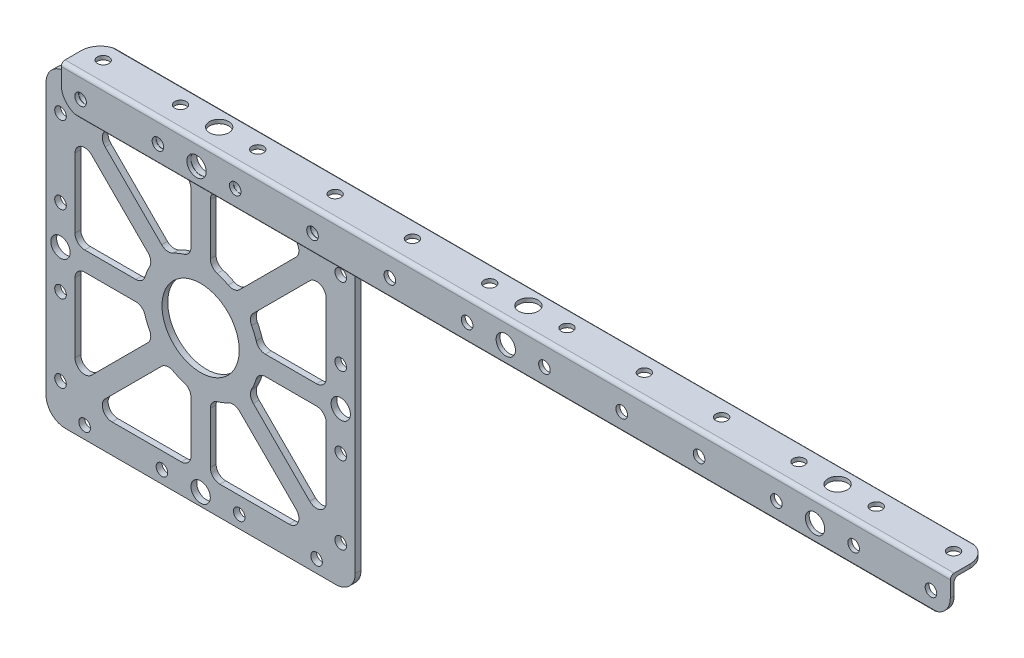
SolidWorks part; units mm, degrees
material "Fibra de vidrio-A"
ref_plane "Alzado" through (0, 0, 0) normal (0, 0, 1) x (1, 0, 0)
ref_plane "Planta" through (0, 0, 0) normal (0, 1, 0) x (1, 0, 0)
ref_plane "Vista lateral" through (0, 0, 0) normal (1, 0, 0) x (0, 0, -1)
sketch "Croquis1" plane through (0, 0, 0) normal (0, 0, 1) x (1, 0, 0)
  line L1 (-35, -40) -> (35, -40)
  line L2 (-40, -35) -> (-40, 35)
  line L3 (-35, 40) -> (35, 40)
  line L4 (40, -35) -> (40, 35)
  line L5 (-40, -40) -> (40, 40) construction
  line L6 (-40, 40) -> (40, -40) construction
  arc A0 (35, 40) -> (40, 35) centre (35, 35) cw
  arc A1 (35, -40) -> (40, -35) centre (35, -35) ccw
  arc A2 (-35, -40) -> (-40, -35) centre (-35, -35) cw
  arc A3 (-40, 35) -> (-35, 40) centre (-35, 35) cw
  point P0 (0, 0)
  dimension "D2" = 5
  dimension "D1" = 80
extrude "Saliente-Extruir1" add sketch "Croquis1" along normal blind 1.5
sketch "Croquis2" plane through (0, 0, 1.5) normal (0, 0, 1) x (1, 0, 0)
  line L0 (0, 0) -> (0, 40) construction
  line L1 (35, 40) -> (-35, 40) construction
  line L2 (0, 0) -> (40, 0) construction
  line L3 (40, -35) -> (40, 35) construction
  line L4 (2.5, 16.7705) -> (2.5, 30)
  line L5 (0, 0) -> (38.5355, 38.5355) construction
  line L6 (10.0908, 13.6263) -> (24.6967, 28.2322)
  line L7 (5, 32.5) -> (22.9289, 32.5)
  line L8 (-10.0908, 13.6263) -> (-24.6967, 28.2322)
  line L9 (-5, 32.5) -> (-22.9289, 32.5)
  line L10 (-2.5, 16.7705) -> (-2.5, 30)
  line L11 (32.5, 5) -> (32.5, 22.9289)
  line L12 (16.7705, 2.5) -> (30, 2.5)
  line L13 (13.6263, 10.0908) -> (28.2322, 24.6967)
  line L14 (16.7705, -2.5) -> (30, -2.5)
  line L15 (32.5, -5) -> (32.5, -22.9289)
  line L16 (13.6263, -10.0908) -> (28.2322, -24.6967)
  line L17 (5, -32.5) -> (22.9289, -32.5)
  line L18 (2.5, -16.7705) -> (2.5, -30)
  line L19 (10.0908, -13.6263) -> (24.6967, -28.2322)
  line L20 (-2.5, -16.7705) -> (-2.5, -30)
  line L21 (-5, -32.5) -> (-22.9289, -32.5)
  line L22 (-10.0908, -13.6263) -> (-24.6967, -28.2322)
  line L23 (-32.5, -5) -> (-32.5, -22.9289)
  line L24 (-16.7705, -2.5) -> (-30, -2.5)
  line L25 (-13.6263, -10.0908) -> (-28.2322, -24.6967)
  line L26 (-16.7705, 2.5) -> (-30, 2.5)
  line L27 (-32.5, 5) -> (-32.5, 22.9289)
  line L28 (-13.6263, 10.0908) -> (-28.2322, 24.6967)
  circle A0 centre (0, 0) radius 10
  arc A1 (7.134, 13.1949) -> (4.2857, 14.3747) centre (0, 0) ccw
  arc A2 (40, 35) -> (35, 40) centre (35, 35) ccw construction
  circle A3 centre (0, 0) radius 15 construction
  arc A4 (2.5, 16.7705) -> (4.2857, 14.3747) centre (5, 16.7705) ccw
  arc A5 (10.0908, 13.6263) -> (7.134, 13.1949) centre (8.323, 15.3941) cw
  arc A6 (24.6967, 28.2322) -> (22.9289, 32.5) centre (22.9289, 30) ccw
  arc A7 (2.5, 30) -> (5, 32.5) centre (5, 30) cw
  arc A8 (-24.6967, 28.2322) -> (-22.9289, 32.5) centre (-22.9289, 30) cw
  arc A9 (-2.5, 30) -> (-5, 32.5) centre (-5, 30) ccw
  arc A10 (-2.5, 16.7705) -> (-4.2857, 14.3747) centre (-5, 16.7705) cw
  arc A11 (-10.0908, 13.6263) -> (-7.134, 13.1949) centre (-8.323, 15.3941) ccw
  arc A12 (-7.134, 13.1949) -> (-4.2857, 14.3747) centre (0, 0) cw
  arc A13 (28.2322, 24.6967) -> (32.5, 22.9289) centre (30, 22.9289) cw
  arc A14 (30, 2.5) -> (32.5, 5) centre (30, 5) ccw
  arc A15 (16.7705, 2.5) -> (14.3747, 4.2857) centre (16.7705, 5) cw
  arc A16 (13.1949, 7.134) -> (14.3747, 4.2857) centre (0, 0) cw
  arc A17 (13.6263, 10.0908) -> (13.1949, 7.134) centre (15.3941, 8.323) ccw
  arc A18 (13.1949, -7.134) -> (14.3747, -4.2857) centre (0, 0) ccw
  arc A19 (13.6263, -10.0908) -> (13.1949, -7.134) centre (15.3941, -8.323) cw
  arc A20 (16.7705, -2.5) -> (14.3747, -4.2857) centre (16.7705, -5) ccw
  arc A21 (30, -2.5) -> (32.5, -5) centre (30, -5) cw
  arc A22 (28.2322, -24.6967) -> (32.5, -22.9289) centre (30, -22.9289) ccw
  arc A23 (24.6967, -28.2322) -> (22.9289, -32.5) centre (22.9289, -30) cw
  arc A24 (2.5, -30) -> (5, -32.5) centre (5, -30) ccw
  arc A25 (2.5, -16.7705) -> (4.2857, -14.3747) centre (5, -16.7705) cw
  arc A26 (7.134, -13.1949) -> (4.2857, -14.3747) centre (0, 0) cw
  arc A27 (10.0908, -13.6263) -> (7.134, -13.1949) centre (8.323, -15.3941) ccw
  arc A28 (-7.134, -13.1949) -> (-4.2857, -14.3747) centre (0, 0) ccw
  arc A29 (-10.0908, -13.6263) -> (-7.134, -13.1949) centre (-8.323, -15.3941) cw
  arc A30 (-2.5, -16.7705) -> (-4.2857, -14.3747) centre (-5, -16.7705) ccw
  arc A31 (-2.5, -30) -> (-5, -32.5) centre (-5, -30) cw
  arc A32 (-24.6967, -28.2322) -> (-22.9289, -32.5) centre (-22.9289, -30) ccw
  arc A33 (-28.2322, -24.6967) -> (-32.5, -22.9289) centre (-30, -22.9289) cw
  arc A34 (-30, -2.5) -> (-32.5, -5) centre (-30, -5) ccw
  arc A35 (-16.7705, -2.5) -> (-14.3747, -4.2857) centre (-16.7705, -5) cw
  arc A36 (-13.1949, -7.134) -> (-14.3747, -4.2857) centre (0, 0) cw
  arc A37 (-13.6263, -10.0908) -> (-13.1949, -7.134) centre (-15.3941, -8.323) ccw
  arc A38 (-13.1949, 7.134) -> (-14.3747, 4.2857) centre (0, 0) ccw
  arc A39 (-13.6263, 10.0908) -> (-13.1949, 7.134) centre (-15.3941, 8.323) cw
  arc A40 (-16.7705, 2.5) -> (-14.3747, 4.2857) centre (-16.7705, 5) ccw
  arc A41 (-30, 2.5) -> (-32.5, 5) centre (-30, 5) cw
  arc A42 (-28.2322, 24.6967) -> (-32.5, 22.9289) centre (-30, 22.9289) ccw
  point P25 (28.9645, 32.5)
  point P28 (2.5, 32.5)
  point P116 (0, 0)
  dimension "D1" = 20
  dimension "D7" = 2.5
  dimension "D2" = 5
  dimension "D3" = 7.5
  dimension "D4" = 2.5
  dimension "D5" = 5
  dimension "D8" = 4
extrude "Cortar-Extruir1" cut sketch "Croquis2" against normal through all
sketch "Croquis3" plane through (0, 0, 1.5) normal (0, 0, 1) x (1, 0, 0)
  line L0 (-36.25, -40) -> (-36.25, 40) construction
  line L1 (-40, 35) -> (-40, -35) construction
  line L2 (-40, 0) -> (-32.5, 0) construction
  line L3 (35, 40) -> (-35, 40) construction
  line L4 (0, -0.825) -> (0, 0.825) construction
  circle A0 centre (-36.25, 30) radius 1.5
  circle A1 centre (-36.25, 10) radius 1.5
  circle A2 centre (-36.25, -10) radius 1.5
  circle A3 centre (-36.25, -30) radius 1.5
  circle A4 centre (36.25, -30) radius 1.5
  circle A5 centre (36.25, -10) radius 1.5
  circle A6 centre (36.25, 10) radius 1.5
  circle A7 centre (36.25, 30) radius 1.5
  circle A8 centre (-36.25, 0) radius 2.5
  circle A9 centre (36.25, 0) radius 2.5
  point P8 (-36.25, 0)
  dimension "D1" = 3
  dimension "D2" = 10
  dimension "D4" = 5
  dimension "D3" = 4
extrude "Cortar-Extruir2" cut sketch "Croquis3" against normal through all
sketch "Croquis5" plane through (0, 0, 0) normal (1, 0, 0) x (0, 0, -1)
  line L0 (0, 32.5) -> (-1.5, 32.5) construction
  line L2 (-0.75, 32.5) -> (-0.75, 35) construction
  line L3 (-1.5, 35) -> (0, 35) construction
  line L4 (-1.55, 32.75) -> (-1.55, 40)
  line L5 (-1.8, 32.5) -> (-2.3, 32.5)
  line L6 (-2.55, 32.75) -> (-2.55, 40.85)
  line L7 (1.05, 32.75) -> (1.05, 40.85)
  line L8 (0.3, 32.5) -> (0.8, 32.5)
  line L9 (0.05, 32.75) -> (0.05, 40)
  line L10 (-1.3, 40.25) -> (-0.2, 40.25)
  line L11 (-2.05, 41.35) -> (0.55, 41.35)
  arc A0 (1.05, 40.85) -> (0.55, 41.35) centre (0.55, 40.85) ccw
  arc A1 (-2.55, 40.85) -> (-2.05, 41.35) centre (-2.05, 40.85) cw
  arc A2 (0.05, 40) -> (-0.2, 40.25) centre (-0.2, 40) ccw
  arc A3 (-1.55, 40) -> (-1.3, 40.25) centre (-1.3, 40) cw
  arc A4 (1.05, 32.75) -> (0.8, 32.5) centre (0.8, 32.75) cw
  arc A5 (0.3, 32.5) -> (0.05, 32.75) centre (0.3, 32.75) cw
  arc A6 (-1.8, 32.5) -> (-1.55, 32.75) centre (-1.8, 32.75) ccw
  arc A7 (-2.3, 32.5) -> (-2.55, 32.75) centre (-2.3, 32.75) cw
  point P16 (1.05, 41.35)
  point P19 (-2.55, 41.35)
  point P22 (0.05, 40.25)
  point P25 (-1.55, 40.25)
  point P28 (1.05, 32.5)
  point P31 (0.05, 32.5)
  point P34 (-1.55, 32.5)
  point P37 (-2.55, 32.5)
  dimension "D5" = 0.5
  dimension "D6" = 0.25
  dimension "D7" = 0.25
  dimension "D1" = 0.8
  dimension "D2" = 7.75
  dimension "D3" = 1
  dimension "D4" = 8.85
extrude "Saliente-Extruir2" add sketch "Croquis5" along normal mid plane 70 separate body
sketch "Croquis4" plane through (0, 0, 1.5) normal (0, 0, 1) x (1, 0, 0)
  line L0 (0, 40) -> (0, 36.75) construction
  line L1 (35, 40) -> (-35, 40) construction
  line L2 (-40, 36.75) -> (40, 36.75) construction
  line L3 (1.98, 0) -> (-1.98, 0) construction
  circle A0 centre (-30, 36.75) radius 1.5
  circle A1 centre (-10, 36.75) radius 1.5
  circle A2 centre (10, 36.75) radius 1.5
  circle A3 centre (30, 36.75) radius 1.5
  circle A4 centre (10, -36.75) radius 1.5
  circle A5 centre (30, -36.75) radius 1.5
  circle A6 centre (-10, -36.75) radius 1.5
  circle A7 centre (-30, -36.75) radius 1.5
  circle A8 centre (0, 36.75) radius 2.5
  circle A9 centre (0, -36.75) radius 2.5
  point P8 (0, 36.75)
  dimension "D3" = 3
  dimension "D6" = 5
  dimension "D1" = 3.25
  dimension "D2" = 40
  dimension "D4" = 10
  dimension "D5" = 4
extrude "Cortar-Extruir3" cut sketch "Croquis4" against normal through all both and the other way through all
fillet "Redondeo1" radius 5 4 edges at (-35, 32.5, -0.55) (35, 32.5, -0.55) (35, 32.5, 2.05) (-35, 32.5, 2.05)
pattern_circular "MatrizC1" count 2 every 90 about axis through (0, 40.8, 0.75) along (1, 0, 0) of bodies 106
combine bodies "Combinar2" bodies to combine 106 107
sketch "Croquis6" plane through (35, 0, 0) normal (1, 0, 0) x (0, 0, -1)
  line L0 (-2.55, 40.85) -> (-2.55, 41.6)
  line L1 (-1.55, 42.6) -> (-0.8, 42.6)
  line L2 (-0.8, 42.6) -> (-0.8, 40.85)
  line L3 (-0.8, 40.85) -> (-2.55, 40.85)
  arc A0 (-2.55, 41.6) -> (-1.55, 42.6) centre (-1.55, 41.6) cw
  dimension "D1" = 1
extrude "Saliente-Extruir3" add sketch "Croquis6" against normal up to surface (70 mm away) up to face at (-35, 40.1525, 0.1025)
sketch "Croquis7" plane through (35, 0, 0) normal (1, 0, 0) x (0, 0, -1)
  line L9 (0.05, 37.5) -> (0.05, 39)
  line L10 (1.05, 40) -> (2.55, 40)
  line L11 (2.55, 40) -> (2.55, 41.6)
  line L12 (2.55, 41.6) -> (-0.55, 41.6)
  line L13 (-1.55, 40.6) -> (-1.55, 37.5)
  line L14 (-1.55, 37.5) -> (0.05, 37.5)
  arc A0 (-0.55, 41.6) -> (-1.55, 40.6) centre (-0.55, 40.6) ccw
  arc A1 (0.05, 39) -> (1.05, 40) centre (1.05, 39) cw
  point P21 (0.05, 40)
  dimension "D1" = 1
extrude "Cortar-Extruir4" cut sketch "Croquis7" against normal through all
delete or keep bodies "Sólido-Eliminar/Conservar 3" bodies 113
sketch "Croquis10" plane through (0, 0, 0) normal (1, 0, 0) x (0, 0, -1)
  line L0 (7.55, 41.85) -> (7.55, 42.35) construction
  line L1 (7.3, 42.6) -> (2.55, 42.6) construction
  line L2 (2.55, 41.6) -> (7.3, 41.6) construction
  line L3 (-2.3, 32.5) -> (-1.8, 32.5) construction
  line L4 (-1.55, 32.75) -> (-1.55, 37.5) construction
  line L5 (-2.55, 37.5) -> (-2.55, 32.75) construction
  line L6 (-1.55, 37.5) -> (-1.55, 40.6) construction
  line L7 (-0.55, 41.6) -> (2.55, 41.6) construction
  line L8 (2.55, 42.6) -> (-1.55, 42.6) construction
  line L9 (-2.55, 41.6) -> (-2.55, 37.5) construction
  line L10 (7.55, 41.85) -> (7.55, 42.35)
  line L11 (7.3, 42.6) -> (2.55, 42.6)
  line L12 (2.55, 41.6) -> (7.3, 41.6)
  line L13 (-2.3, 32.5) -> (-1.8, 32.5)
  line L14 (-1.55, 32.75) -> (-1.55, 37.5)
  line L15 (-2.55, 37.5) -> (-2.55, 32.75)
  line L16 (-1.55, 37.5) -> (-1.55, 40.6)
  line L17 (-0.55, 41.6) -> (2.55, 41.6)
  line L18 (2.55, 42.6) -> (-1.55, 42.6)
  line L19 (-2.55, 41.6) -> (-2.55, 37.5)
  arc A0 (7.3, 41.6) -> (7.55, 41.85) centre (7.3, 41.85) ccw construction
  arc A1 (7.55, 42.35) -> (7.3, 42.6) centre (7.3, 42.35) ccw construction
  arc A2 (-2.55, 32.75) -> (-2.3, 32.5) centre (-2.3, 32.75) ccw construction
  arc A3 (-1.8, 32.5) -> (-1.55, 32.75) centre (-1.8, 32.75) ccw construction
  arc A4 (-0.55, 41.6) -> (-1.55, 40.6) centre (-0.55, 40.6) ccw construction
  arc A5 (-1.55, 42.6) -> (-2.55, 41.6) centre (-1.55, 41.6) ccw construction
  arc A6 (7.3, 41.6) -> (7.55, 41.85) centre (7.3, 41.85) ccw
  arc A7 (7.55, 42.35) -> (7.3, 42.6) centre (7.3, 42.35) ccw
  arc A8 (-2.55, 32.75) -> (-2.3, 32.5) centre (-2.3, 32.75) ccw
  arc A9 (-1.8, 32.5) -> (-1.55, 32.75) centre (-1.8, 32.75) ccw
  arc A10 (-0.55, 41.6) -> (-1.55, 40.6) centre (-0.55, 40.6) ccw
  arc A11 (-1.55, 42.6) -> (-2.55, 41.6) centre (-1.55, 41.6) ccw
extrude "Saliente-Extruir4" add sketch "Croquis10" along normal blind 195
fillet "Redondeo2" radius 5 2 edges at (195, 32.5, 2.05) (195, 42.1, -7.55)
sketch "Croquis11" plane through (0, 42.6, 0) normal (0, 1, 0) x (1, 0, 0)
  line L0 (-30, 3.3) -> (-35, 3.3) construction
  line L2 (0, 5.8) -> (0, 0.8) construction
  line L3 (190, 3.3) -> (195, 3.3) construction
  circle A0 centre (-30, 3.3) radius 1.5 construction
  circle A1 centre (-30, 3.3) radius 1.5
  circle A2 centre (-10, 3.3) radius 1.5
  circle A3 centre (10, 3.3) radius 1.5
  circle A4 centre (30, 3.3) radius 1.5
  circle A5 centre (50, 3.3) radius 1.5
  circle A6 centre (70, 3.3) radius 1.5
  circle A7 centre (90, 3.3) radius 1.5
  circle A8 centre (110, 3.3) radius 1.5
  circle A9 centre (130, 3.3) radius 1.5
  circle A10 centre (150, 3.3) radius 1.5
  circle A11 centre (170, 3.3) radius 1.5
  circle A12 centre (190, 3.3) radius 1.5
  circle A14 centre (0, 3.3) radius 2.5
  circle A15 centre (80, 3.3) radius 2.5
  circle A16 centre (160, 3.3) radius 2.5
  dimension "D4" = 3
  dimension "D1" = 5
  dimension "D5" = 5
extrude "Cortar-Extruir5" cut sketch "Croquis11" against normal up to next (1 mm away)
sketch "Croquis12" plane through (0, 0, 2.55) normal (0, 0, 1) x (1, 0, 0)
  line L0 (-30, 36.75) -> (-35, 36.75) construction
  line L1 (0, 39.25) -> (0, 34.25) construction
  circle A0 centre (-30, 36.75) radius 1.5 construction
  circle A1 centre (-30, 36.75) radius 1.5
  circle A2 centre (-10, 36.75) radius 1.5
  circle A3 centre (10, 36.75) radius 1.5
  circle A4 centre (30, 36.75) radius 1.5
  circle A5 centre (50, 36.75) radius 1.5
  circle A6 centre (70, 36.75) radius 1.5
  circle A7 centre (90, 36.75) radius 1.5
  circle A8 centre (110, 36.75) radius 1.5
  circle A9 centre (130, 36.75) radius 1.5
  circle A10 centre (150, 36.75) radius 1.5
  circle A11 centre (170, 36.75) radius 1.5
  circle A12 centre (190, 36.75) radius 1.5
  circle A13 centre (0, 36.75) radius 2.5
  circle A14 centre (80, 36.75) radius 2.5
  circle A15 centre (160, 36.75) radius 2.5
  dimension "D3" = 3
  dimension "D1" = 5
  dimension "D2" = 12
extrude "Cortar-Extruir6" cut sketch "Croquis12" against normal up to next (1 mm away)
